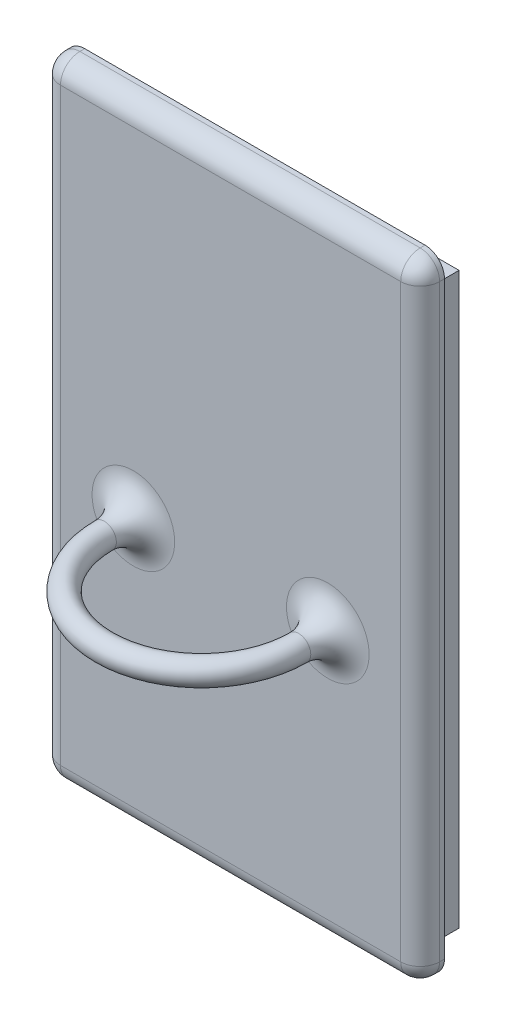
SolidWorks part; units mm, degrees
ref_plane "Front Plane" through (0, 0, 0) normal (0, 0, 1) x (1, 0, 0)
ref_plane "Top Plane" through (0, 0, 0) normal (0, 1, 0) x (1, 0, 0)
ref_plane "Right Plane" through (0, 0, 0) normal (1, 0, 0) x (0, 0, -1)
sketch "Sketch1" plane through (0, 0, 0) normal (0, 0, 1) x (1, 0, 0)
  line L1 (-24.765, -37.211) -> (24.765, -37.211)
  line L2 (-24.765, -37.211) -> (-24.765, -18.5704)
  line L3 (-24.765, 37.211) -> (24.765, 37.211)
  line L4 (24.765, -37.211) -> (24.765, -18.5704)
  line L5 (-24.765, -37.211) -> (24.765, 37.211) construction
  line L6 (-24.765, 37.211) -> (24.765, -37.211) construction
  line L9 (-24.765, 0.679) -> (-24.765, 37.211)
  line L10 (0, 0) -> (0, 16.5021) construction
  line L14 (24.765, 0.679) -> (24.765, 37.211)
  line L15 (-24.765, 0.679) -> (-24.765, -18.5704)
  line L16 (24.765, -18.5704) -> (24.765, 0.679)
  point P0 (0, 0)
  dimension "D1" = 74.422
  dimension "D2" = 49.53
extrude "Boss-Extrude1" add sketch "Sketch1" along normal blind 3.175
sketch "Sketch6" plane through (0, 0, 3.175) normal (0, 0, 1) x (1, 0, 0)
  line L0 (-24.765, -5.7707) -> (24.765, -5.7707) construction
  line L4 (-24.765, 37.211) -> (-24.765, -37.211) construction
  line L5 (24.765, -37.211) -> (24.765, 37.211) construction
  dimension "D1" = 0
  dimension "D2" = 0
ref_plane "Plane1" through (0, -5.7707, 0) normal (0, 1, 0) x (1, 0, 0)
sketch "Sketch7" plane through (0, -5.7707, 0) normal (0, 1, 0) x (1, 0, 0)
  line L0 (0, 0) -> (0, -3.175) construction
  line L1 (-24.765, -3.175) -> (24.765, -3.175) construction
  line L2 (12.7, -3.175) -> (-12.7, -3.175) construction
  line L3 (-12.7, -3.175) -> (-12.7, -6.985)
  line L4 (0, -6.985) -> (0, -23.813) construction
  line L5 (12.7, -3.175) -> (12.7, -6.985)
  arc A0 (-12.7, -6.985) -> (12.7, -6.985) centre (0, -6.985) ccw
  dimension "D1" = 12.7
  dimension "D2" = 3.81
sweep "Sweep1" add path "Sketch7" circular profile diameter 3.175 parameters "D3"=3.175
fillet "Fillet1" radius 3.81 2 edges at (14.2875, -5.7707, 3.175) (-14.2875, -5.7707, 3.175)
sketch "Sketch14" plane through (0, 0, 3.175) normal (0, 0, 1) x (1, 0, 0)
  line L0 (24.765, -37.211) -> (24.765, 37.211) construction
  line L1 (-24.765, -37.211) -> (24.765, -37.211)
  line L2 (-24.765, -37.211) -> (-24.765, -41.021)
  line L3 (-24.765, -41.021) -> (24.765, -41.021)
  line L4 (24.765, -37.211) -> (24.765, -41.021)
  line L5 (-24.765, 37.211) -> (24.765, 37.211)
  line L6 (-24.765, 37.211) -> (-24.765, 41.021)
  line L7 (-24.765, 41.021) -> (24.765, 41.021)
  line L8 (24.765, 37.211) -> (24.765, 41.021)
  line L9 (24.765, -37.211) -> (24.765, 37.211) construction
  dimension "D1" = 3.81
  dimension "D2" = 3.81
  dimension "D3" = 0
  dimension "D4" = 0
extrude "Boss-Extrude4" add sketch "Sketch14" against normal up to surface (3.175 mm away) up to face at (0, 0, 0)
fillet "Fillet2" radius 2.54 4 edges at (-24.765, 0, 3.175) (24.765, 0, 3.175) (0, 41.021, 3.175) (0, -41.021, 3.175)
fillet "Fillet4" radius 2.54 8 edges at (24.765, 41.021, 0.3175) (-24.765, 41.021, 0.3175) (-24.765, -41.021, 0.3175) (24.0211, -40.2771, 2.4311) (24.0211, 40.2771, 2.4311) (-24.0211, 40.2771, 2.4311) (-24.0211, -40.2771, 2.4311) (24.765, -41.021, 0.3175)
sketch "Sketch15" plane through (0, 0, 0) normal (0, 0, -1) x (-1, 0, 0)
  line L17 (-20.32, -34.036) -> (-20.32, 34.036)
  line L18 (-23.495, -37.211) -> (23.495, -37.211)
  line L23 (-23.495, -37.211) -> (-23.495, 37.211)
  line L24 (-23.495, 37.211) -> (23.495, 37.211)
  line L25 (23.495, -37.211) -> (23.495, 37.211)
  line L26 (-23.495, -37.211) -> (23.495, 37.211) construction
  line L27 (-23.495, 37.211) -> (23.495, -37.211) construction
  line L28 (-20.32, 34.036) -> (20.32, 34.036)
  line L29 (20.32, -34.036) -> (20.32, 34.036)
  line L30 (-20.32, -34.036) -> (20.32, -34.036)
  point P0 (0, 0)
  dimension "D1" = 46.99
  dimension "D2" = 74.422
  dimension "D3" = 3.175
extrude "Boss-Extrude6" add sketch "Sketch15" along normal blind 3.175
